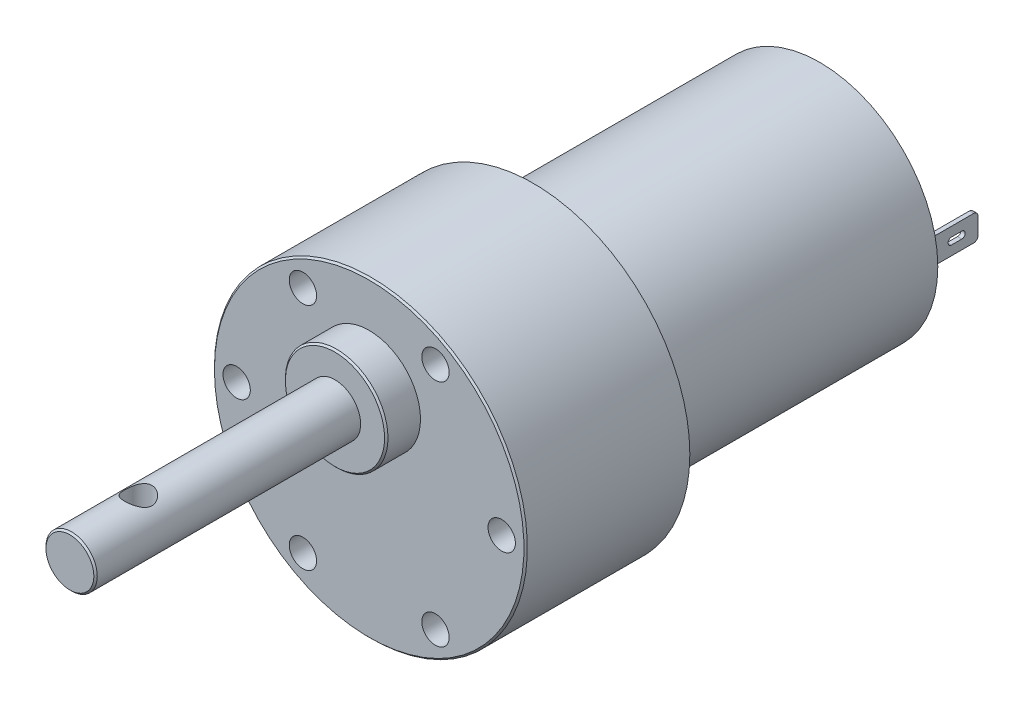
SolidWorks part; units mm, degrees
material "ABS"
ref_plane "Front Plane" through (0, 0, 0) normal (0, 0, 1) x (1, 0, 0)
ref_plane "Top Plane" through (0, 0, 0) normal (0, 1, 0) x (1, 0, 0)
ref_plane "Right Plane" through (0, 0, 0) normal (1, 0, 0) x (0, 0, -1)
sketch "Sketch1" plane through (0, 0, 0) normal (0, 0, 1) x (1, 0, 0)
  circle A0 centre (0, 0) radius 18.3
  dimension "D1" = 36.6
extrude "Boss-Extrude1" add sketch "Sketch1" along normal blind 19.2
sketch "Sketch2" plane through (0, 0, 19.2) normal (0, 0, 1) x (1, 0, 0)
  line L0 (-18.3, 0) -> (18.3, 0) construction
  line L1 (0, 18.3) -> (0, -18.3) construction
  line L2 (11.1332, 19.2832) -> (-10.7359, -18.5952) construction
  line L3 (-11.3747, 19.7016) -> (11.6905, -20.2486) construction
  circle A0 centre (0, 0) radius 18.3 construction
  circle A1 centre (0, 0) radius 15.5 construction
  circle A2 centre (-7.75, 13.4234) radius 1.6
  circle A3 centre (7.75, 13.4234) radius 1.6
  circle A4 centre (-15.5, 0) radius 1.6
  circle A5 centre (-7.75, -13.4234) radius 1.6
  circle A6 centre (7.75, -13.4234) radius 1.6
  circle A7 centre (15.5, 0) radius 1.6
  dimension "D3" = 31
  dimension "D4" = 3.2
  dimension "D1" = 120
  dimension "D2" = 120
extrude "Cut-Extrude1" cut sketch "Sketch2" against normal blind 3.5
sketch "Sketch3" plane through (0, 0, 19.2) normal (0, 0, 1) x (1, 0, 0)
  line L0 (0, 0) -> (0, 18.3) construction
  circle A0 centre (0, 0) radius 18.3 construction
  circle A1 centre (0, 7) radius 6
  circle A2 centre (0, 7) radius 3
  dimension "D1" = 12
  dimension "D3" = 6
  dimension "D2" = 7
extrude "Boss-Extrude2" add sketch "Sketch3" along normal blind 35 contours A2 L0 | L0 A2 region at (-1.2732, 7, 19.2) region at (1.2732, 7, 19.2)
extrude "Boss-Extrude3" add sketch "Sketch3<3>" along normal blind 4 contours A1 L0 A2 | L0 A1 A2 region at (-5.8658, 7, 19.2) region at (0.1342, 2.5, 19.2)
sketch "Sketch3<3>" plane through (0, 0, 19.2) normal (0, 0, 1) x (1, 0, 0) same geometry as "Sketch3"
sketch "Sketch4" plane through (0, 0, 0) normal (0, 0, -1) x (-1, 0, 0)
  circle A0 centre (0, 0) radius 13.8
  dimension "D1" = 27.6
extrude "Boss-Extrude4" add sketch "Sketch4" along normal blind 33.5
sketch "Sketch5" plane through (0, 0, -33.5) normal (0, 0, -1) x (-1, 0, 0)
  line L0 (-13.8, 0) -> (13.8, 0) construction
  circle A0 centre (0, 0) radius 5
  circle A1 centre (0, 0) radius 13.8 construction
  dimension "D1" = 10
extrude "Boss-Extrude5" add sketch "Sketch5" along normal blind 3
sketch "Sketch6" plane through (0, 0, -36.5) normal (0, 0, -1) x (-1, 0, 0)
  circle A0 centre (0, 0) radius 1
  dimension "D1" = 2
extrude "Boss-Extrude6" add sketch "Sketch6" along normal blind 5
sketch "Sketch7" plane through (0, 0, -33.5) normal (0, 0, -1) x (-1, 0, 0)
  line L0 (-13.8, 0) -> (13.8, 0) construction
  line L1 (0, 0) -> (0, -10.7163) construction
  line L2 (-12, 1.5) -> (-11.5, 1.5)
  line L3 (-12, 1.5) -> (-12, -1.5)
  line L4 (-12, -1.5) -> (-11.5, -1.5)
  line L5 (-11.5, 1.5) -> (-11.5, -1.5)
  line L6 (12, 1.5) -> (11.5, 1.5)
  line L7 (12, -1.5) -> (11.5, -1.5)
  line L8 (12, 1.5) -> (12, -1.5)
  line L9 (11.5, 1.5) -> (11.5, -1.5)
  circle A0 centre (0, 0) radius 13.8 construction
  circle A1 centre (0, 0) radius 13.8 construction
  dimension "D1" = 3
  dimension "D2" = 1.5
  dimension "D3" = 0.5
  dimension "D4" = 11.5
extrude "Boss-Extrude7" add sketch "Sketch7" along normal blind 6.5
sketch "Sketch8" plane through (12, 0, 0) normal (1, 0, 0) x (0, 0, -1)
  line L0 (38.1, 0) -> (36.9, 0) construction
  line L1 (38.1, -0.4) -> (36.9, -0.4)
  line L2 (38.1, 0.4) -> (36.9, 0.4)
  line L3 (38.1, 0) -> (40, 0) construction
  line L4 (40, 1.5) -> (40, -1.5) construction
  line L5 (33.5, -13.8) -> (33.5, 13.8) construction
  arc A0 (38.1, -0.4) -> (38.1, 0.4) centre (38.1, 0) ccw
  arc A1 (36.9, 0.4) -> (36.9, -0.4) centre (36.9, 0) ccw
  point P2 (37.5, 0)
  dimension "D3" = 0.4
  dimension "D1" = 1.2
  dimension "D2" = 4
extrude "Cut-Extrude2" cut sketch "Sketch8" against normal blind 0.5
mirror "Mirror2" about plane through (0, 0, 0) normal (1, 0, 0) of "Cut-Extrude2"
fillet "Fillet1" radius 0.5 4 edges at (-11.75, 1.5, -40) (-11.75, -1.5, -40) (11.75, 1.5, -40) (11.75, -1.5, -40)
chamfer "Chamfer1" distance 0.2 angle 45 3 edges at (18.3, 0, 19.2) (6, 7, 23.2) (3, 7, 54.2)
ref_plane "Plane1" through (0, 7, 0) normal (0, 1, 0) x (1, 0, 0)
sketch "Sketch9" plane through (0, 7, 0) normal (0, 1, 0) x (1, 0, 0)
  line L0 (0, -54) -> (0, -23.2) construction
  line L1 (3, -54) -> (-3, -54) construction
  line L2 (-2.8, -54.2) -> (2.8, -54.2) construction
  line L3 (-3, -23.2) -> (3, -23.2) construction
  circle A0 centre (0, -46.2) radius 1.6
  dimension "D1" = 3.2
  dimension "D2" = 8
extrude "Cut-Extrude3" cut sketch "Sketch9" against normal through all and the other way through all
